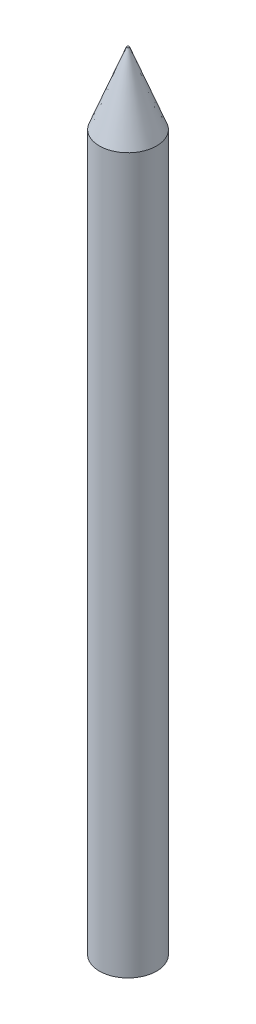
SolidWorks part; units mm, degrees
ref_plane "Ebene vorne" through (0, 0, 0) normal (0, 0, 1) x (1, 0, 0)
ref_plane "Ebene oben" through (0, 0, 0) normal (0, 1, 0) x (1, 0, 0)
ref_plane "Ebene rechts" through (0, 0, 0) normal (1, 0, 0) x (0, 0, -1)
sketch "Sketch1" plane through (0, 0, 0) normal (0, 1, 0) x (1, 0, 0)
  circle A0 centre (0, 0) radius 2
  dimension "D1" = 4
extrude "Boss-Extrude1" add sketch "Sketch1" along normal blind 50
sketch "Sketch2" plane through (0, 0, 0) normal (0, 0, 1) x (1, 0, 0)
  line L0 (0, 55) -> (0, 50)
  line L1 (0, 50) -> (2, 50)
  line L2 (0, 55) -> (0.0785, 55)
  line L3 (0.0785, 55) -> (2, 50)
  line L4 (2, 50) -> (-2, 50) construction
  line L5 (-2, 50) -> (2, 50) construction
  point P3 (0, 0)
  point P8 (0, 50)
  dimension "D1" = 5
revolve "Revolve1" add sketch "Sketch2" angle 360 about L0
